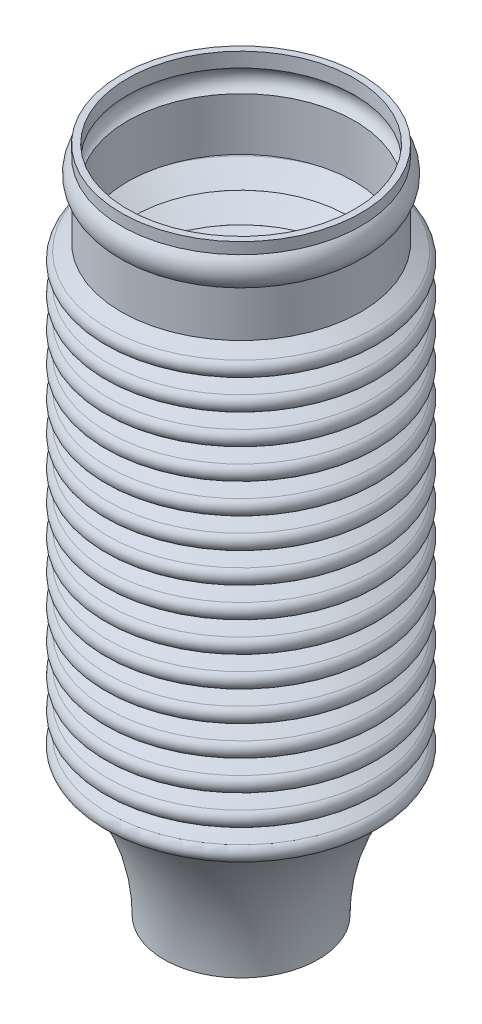
SolidWorks part; units mm, degrees
ref_plane "前视基准面" through (0, 0, 0) normal (0, 0, 1) x (1, 0, 0)
ref_plane "上视基准面" through (0, 0, 0) normal (0, 1, 0) x (1, 0, 0)
ref_plane "右视基准面" through (0, 0, 0) normal (1, 0, 0) x (0, 0, -1)
other "Configuration Table"
sketch "草图1" plane through (0, 0, 0) normal (0, 0, 1) x (1, 0, 0)
  line L0 (0, 0) -> (18, 0)
  line L1 (28, 30.9839) -> (0, 30.9839)
  line L2 (0, 30.9839) -> (0, 0)
  arc A0 (28, 30.9839) -> (18, 0) centre (71, 0) ccw
  dimension "D3" = 53
  dimension "D1" = 28
  dimension "D2" = 18
revolve "旋转1" add sketch "草图1" angle 360 about L2
sketch "草图2" plane through (0, 0, 0) normal (0, 0, 1) x (1, 0, 0)
  line L0 (0, 37.9839) -> (0, 30.9839)
  line L1 (28, 30.9839) -> (-28, 30.9839) construction
  line L3 (-28, 30.9839) -> (-31.1443, 32.7371)
  line L4 (-28, 37.9839) -> (-31.1443, 36.2307)
  line L7 (-28, 37.9839) -> (0, 37.9839)
  line L8 (0, 30.9839) -> (0, 40.2403) construction
  line L9 (-28, 30.9839) -> (0, 30.9839)
  arc A0 (-31.1443, 36.2307) -> (-31.1443, 32.7371) centre (-30.1703, 34.4839) ccw
  point P10 (-29.5721, 37.1073)
  dimension "D3" = 2
  dimension "D1" = 3.6
  dimension "D2" = 7
  dimension "D4" = 3.5
revolve "旋转3" add sketch "草图2" angle 360 about L8
pattern_linear "阵列(线性)1" count 15 spacing 7 along (0, 1, 0) of "旋转3"
sketch "草图3" plane through (0, 0, 0) normal (0, 0, 1) x (1, 0, 0)
  line L0 (0, 135.9839) -> (28, 135.9839)
  line L1 (28, 135.9839) -> (-28, 135.9839) construction
  line L2 (28, 135.9839) -> (28, 146.6298)
  line L3 (28, 155.9839) -> (0, 155.9839)
  line L4 (0, 155.9839) -> (0, 135.9839)
  line L5 (28, 153.338) -> (28, 155.9839)
  arc A0 (28, 153.338) -> (28, 146.6298) centre (25, 149.9839) cw
  point P11 (22.8325, 155.9839)
  dimension "D3" = 4.5
  dimension "D1" = 28
  dimension "D2" = 20
  dimension "D4" = 3
  dimension "D5" = 6
revolve "旋转4" add sketch "草图3" angle 360 about L4
shell "抽壳1" thickness 1.5 removed face at (-28, 155.9839, 0) removed face at (-18, 0, 0)
